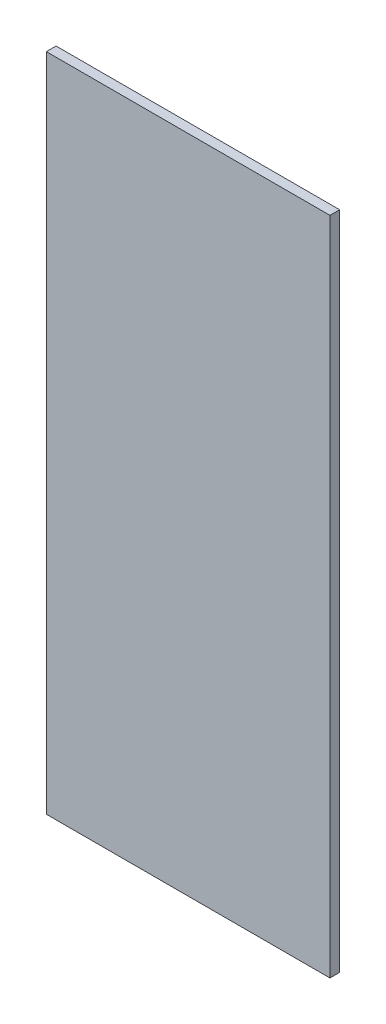
SolidWorks part; units mm, degrees
material "PC High Viscosity"
ref_plane "Front Plane" through (0, 0, 0) normal (0, 0, 1) x (1, 0, 0)
ref_plane "Top Plane" through (0, 0, 0) normal (0, 1, 0) x (1, 0, 0)
ref_plane "Right Plane" through (0, 0, 0) normal (1, 0, 0) x (0, 0, -1)
sketch "Sketch1" plane through (0, 0, 0) normal (0, 0, 1) x (1, 0, 0)
  line L1 (-73, -170) -> (73, -170)
  line L2 (-73, -170) -> (-73, 170)
  line L3 (-73, 170) -> (73, 170)
  line L4 (73, -170) -> (73, 170)
  line L5 (-73, -170) -> (73, 170) construction
  line L6 (-73, 170) -> (73, -170) construction
  point P0 (0, 0)
  dimension "D1" = 146
  dimension "D2" = 340
extrude "Boss-Extrude1" add sketch "Sketch1" along normal mid plane 5
sketch "Sketch2" [suppressed] plane through (0, 0, 2.5) normal (0, 0, 1) x (1, 0, 0)
  line L0 (106, 171) -> (104, 171) construction
  line L1 (-155.214, 211.8255) -> (203.9552, 211.8255)
  line L2 (-155.214, 211.8255) -> (-155.214, 171)
  line L3 (-155.214, 171) -> (203.9552, 171)
  line L4 (203.9552, 211.8255) -> (203.9552, 171)
extrude "Cut-Extrude1" [suppressed] cut sketch "Sketch2" against normal through all
